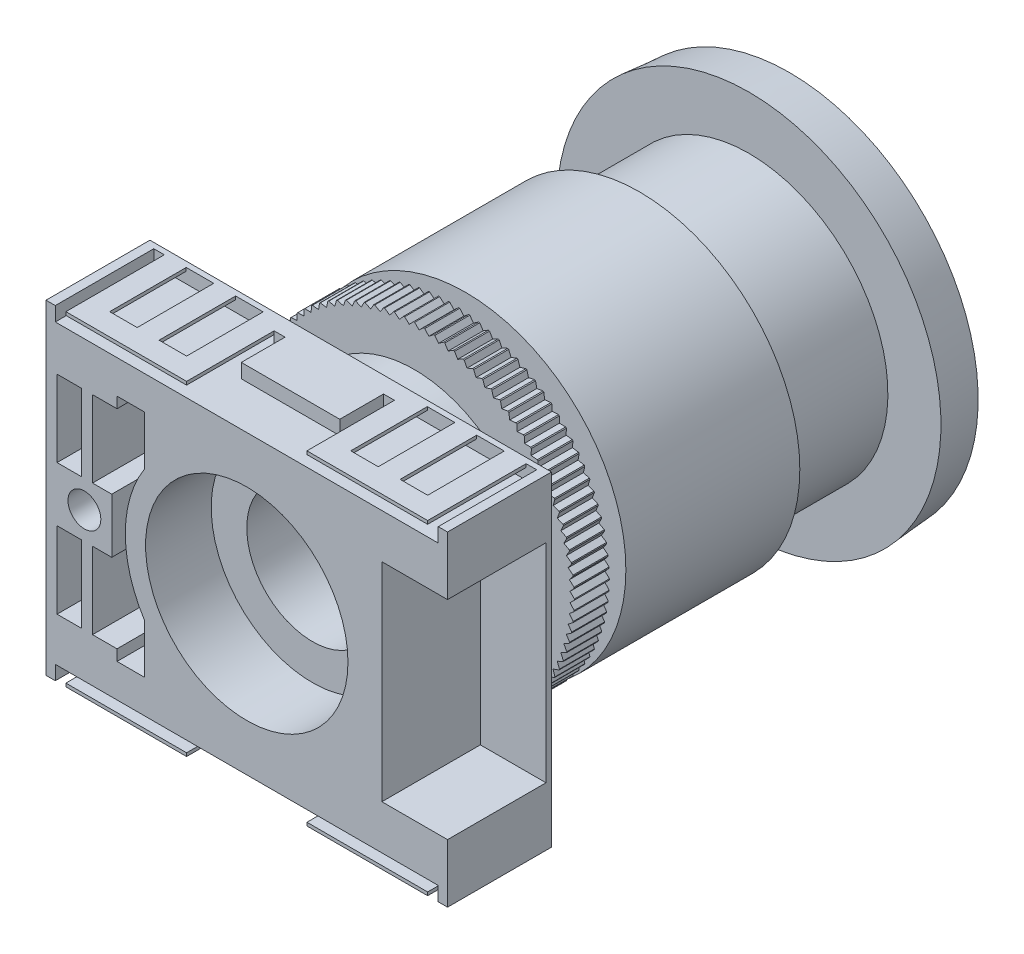
SolidWorks part; units mm, degrees
material "ABS"
ref_plane "正面" through (0, 0, 0) normal (0, 0, 1) x (1, 0, 0)
ref_plane "平面" through (0, 0, 0) normal (0, 1, 0) x (1, 0, 0)
ref_plane "右側面" through (0, 0, 0) normal (1, 0, 0) x (0, 0, -1)
sketch "ｽｹｯﾁ2" plane through (0, 0, 0) normal (1, 0, 0) x (0, 0, -1)
  line L0 (0, 0) -> (-50.6, 0) construction
  line L1 (-30.3, 0) -> (-30.3, 14.65)
  line L2 (-30.3, 14.65) -> (-14.4, 14.65)
  line L3 (-1.9, 15.9) -> (-0.7, 15.9)
  line L4 (-14.4, 12.8) -> (-14.4, 14.65)
  line L5 (-14.4, 12.7) -> (-4.4, 12.7)
  line L6 (-4.4, 12.7) -> (-4.4, 17.55)
  line L7 (-4.4, 17.55) -> (-0.7, 17.55) construction
  line L8 (-0.7, -13.9) -> (-0.7, 13.9) construction
  line L9 (-0.7, 17.25) -> (-4.4, 17.55)
  line L10 (-1.9, 13.9) -> (-0.7, 13.9)
  line L11 (-0.7, 15.9) -> (-0.7, 17.25)
  line L12 (-5.9513, 13.9) -> (1.3937, 13.9) construction
  line L13 (-5.9513, 15.9) -> (1.3937, 15.9) construction
  line L14 (-14.4, 12.7) -> (-28.4, 12.7)
  line L15 (-28.4, 12.7) -> (-28.4, 12.8)
  line L16 (-28.4, 12.8) -> (-14.4, 12.8)
  line L17 (0, 0) -> (-30.3, 0)
  arc A0 (-1.9, 15.9) -> (-1.9, 13.9) centre (-1.9, 14.9) ccw
  arc A1 (-0.7, 13.9) -> (0, 0) centre (-138.3571, 0) cw
  point P22 (-0.7, 0)
  dimension "D1" = 20.3
  dimension "D2" = 50.6
  dimension "D3" = 15.9
  dimension "D4" = 17.55
  dimension "D5" = 2
  dimension "D6" = 3.7
  dimension "D7" = 1.2
revolve "回転1" add sketch "ｽｹｯﾁ2" angle 360 about L0
sketch "ｽｹｯﾁ3" plane through (0, 0, 30.3) normal (0, 0, 1) x (1, 0, 0)
  circle A0 centre (0, 0) radius 10.9
extrude "ﾎﾞｽ - 押し出し1" add sketch "ｽｹｯﾁ3" along normal blind 20
sketch "ｽｹｯﾁ4" plane through (0, 0, 50.3) normal (0, 0, 1) x (1, 0, 0)
  circle A0 centre (0, 0) radius 6
extrude "ｶｯﾄ - 押し出し1" cut sketch "ｽｹｯﾁ4" against normal blind 49
sketch "ｽｹｯﾁ5" plane through (0, 0, 50.3) normal (0, 0, 1) x (1, 0, 0)
  circle A0 centre (0, 0) radius 9.25
extrude "ｶｯﾄ - 押し出し2" cut sketch "ｽｹｯﾁ5" against normal blind 6
ref_plane "平面2" through (0, 0, 31.8) normal (0, 0, 1) x (1, 0, 0)
sketch "ｽｹｯﾁ7" plane through (0, 0, 31.8) normal (0, 0, 1) x (1, 0, 0)
  circle A0 centre (0, 0) radius 14.7
  circle A1 centre (0, 0) radius 10.9
extrude "ﾎﾞｽ - 押し出し2" add sketch "ｽｹｯﾁ7" along normal blind 3.2
sketch "ｽｹｯﾁ9" plane through (0, 0, 35) normal (0, 0, 1) x (1, 0, 0)
  line L0 (0, 0) -> (0, 14.7) construction
  line L1 (0, 0) -> (0.923, 14.671) construction
  line L2 (0, 0) -> (0.4617, 14.6927) construction
  line L3 (0.4617, 14.6927) -> (0.4476, 14.243)
  line L4 (0.4476, 14.243) -> (0, 14.7)
  line L5 (0.4476, 14.243) -> (0.923, 14.671)
  circle A0 centre (0, 0) radius 14.7 construction
  arc A1 (0, 14.7) -> (0.923, 14.671) centre (0, 0) cw
  circle M1 centre (0, 0) radius 14.7
  dimension "D1" = 3.6
extrude "ｶｯﾄ - 押し出し3" cut sketch "ｽｹｯﾁ9" along direction (0, 0, 1) on the side against the normal up to next (3.2 mm away) contours L4 L3 M1 | L3 L5 M1 region at (0.6112, 14.5364, 35) region at (0.3027, 14.5461, 35)
pattern_circular "円形ﾊﾟﾀｰﾝ1" count 100 over 360 about axis through (0, 0, 35) along (0, 0, 1) of "ｶｯﾄ - 押し出し3"
sketch "ｽｹｯﾁ10" plane through (0, 0, 35) normal (0, 0, 1) x (1, 0, 0)
  circle A0 centre (0, 0) radius 14.65
extrude "ｶｯﾄ - 押し出し4" cut sketch "ｽｹｯﾁ10" against normal blind 3.2 flip side to cut
sketch "ｽｹｯﾁ11" plane through (0, 0, 50.3) normal (0, 0, 1) x (1, 0, 0)
  line L1 (18.35, 14.85) -> (-18.35, 14.85)
  line L2 (18.35, 14.85) -> (18.35, -14.85)
  line L3 (18.35, -14.85) -> (-18.35, -14.85)
  line L4 (-18.35, 14.85) -> (-18.35, -14.85)
  line L5 (18.35, 14.85) -> (-18.35, -14.85) construction
  line L6 (18.35, -14.85) -> (-18.35, 14.85) construction
  circle A0 centre (0, 0) radius 10.9 construction
  circle A1 centre (0, 0) radius 10.9
  point P0 (0, 0)
extrude "ﾎﾞｽ - 押し出し3" add sketch "ｽｹｯﾁ11" against normal blind 9.5
sketch "ｽｹｯﾁ13" plane through (0, 0, 50.3) normal (0, 0, 1) x (1, 0, 0)
  line L1 (18.35, 14.85) -> (-18.35, 14.85) construction
  line L2 (-17.5, 14.55) -> (-17.5, 13.55)
  line L3 (-17.5, 13.55) -> (17.5, 13.55)
  line L4 (17.5, 14.55) -> (17.5, 13.55)
  line L5 (-5.5, 16.15) -> (5.5, 16.15)
  line L6 (-0.5843, 13.55) -> (-9.5843, 13.55)
  line L7 (17.5, 14.55) -> (5.5, 14.55)
  line L8 (-5.5, 16.15) -> (-5.5, 14.55)
  line L9 (-5.5, 13.55) -> (5.5, 13.55)
  line L10 (5.5, 16.15) -> (5.5, 14.55)
  line L11 (-5.5, 14.55) -> (-17.5, 14.55)
  line L12 (-5.5, 16.15) -> (5.5, 13.55) construction
  line L13 (-5.5, 13.55) -> (5.5, 16.15) construction
  point P0 (0, 14.85)
extrude "ｶｯﾄ - 押し出し5" cut sketch "ｽｹｯﾁ13" against normal blind 9 contours L3 L4 L7 L10 L5 L8 L11 L2
sketch "ｽｹｯﾁ15" plane through (0, 13.55, 0) normal (0, 1, 0) x (-1, 0, 0)
  line L0 (-5.5, 41.3) -> (5.5, 41.3)
  line L1 (5.5, 41.3) -> (5.5, 42.3)
  line L2 (5.5, 41.3) -> (5.5, 50.3) construction
  line L3 (5.5, 42.3) -> (4.5, 42.3)
  line L4 (4.5, 42.3) -> (4.5, 46.3)
  line L5 (4.5, 46.3) -> (-4.5, 46.3)
  line L6 (-4.5, 46.3) -> (-4.5, 42.3)
  line L7 (-4.5, 42.3) -> (-5.5, 42.3)
  line L8 (-5.5, 41.3) -> (-5.5, 50.3) construction
  line L9 (-5.5, 42.3) -> (-5.5, 41.3)
extrude "ﾎﾞｽ - 押し出し5" add sketch "ｽｹｯﾁ15" along normal up to surface (1.3 mm away) up to face at (0, 14.85, 45.675)
sketch "ｽｹｯﾁ16" plane through (0, 14.85, 0) normal (0, 1, 0) x (1, 0, 0)
  line L4 (-7.5, -48.3) -> (-10.0166, -48.3)
  line L5 (18.35, -41.3) -> (-18.35, -41.3)
  line L6 (-7.5, -48.3) -> (-7.5, -42.3)
  line L7 (-16.35, -48.3) -> (-7.5, -48.3)
  line L8 (-16.35, -40.8) -> (-16.35, -48.3)
  line L9 (-7.5, -48.3) -> (-7.5, -41.3)
  line L10 (-14.5331, -48.3) -> (-12.0166, -48.3)
  line L11 (-16.5331, -50.3) -> (-17.5, -50.3)
  line L12 (-7.5, -41.3) -> (-10.0166, -41.3)
  line L19 (-14.5331, -48.3) -> (-14.5331, -41.3)
  line L20 (-12.0166, -41.3) -> (-14.5331, -41.3)
  line L21 (-16.5331, -50.3) -> (-16.5331, -41.3)
  line L22 (-5.5, -50.3) -> (-16.5331, -50.3) construction
  line L23 (-5.5, -50.3) -> (-5.5, -41.3) construction
  line L24 (-12.0166, -48.3) -> (-14.5331, -48.3)
  line L25 (-10.0166, -41.3) -> (-10.0166, -48.3)
  line L26 (-17.5, -50.3) -> (-17.5, -41.3)
  line L27 (-12.0166, -41.3) -> (-12.0166, -48.3)
  line L28 (-17.5, -41.3) -> (-16.5331, -41.3)
  line L30 (-10.0166, -48.3) -> (-7.5, -48.3)
  line L31 (-7.5, -48.3) -> (-14.5331, -48.3) construction
  line M16 (-18.35, -50.3) -> (-5.5, -50.3)
  dimension "D3" = 2
  dimension "D1" = 2
  dimension "D2" = 0.5
extrude "ｶｯﾄ - 押し出し6" cut sketch "ｽｹｯﾁ16" against normal up to next contours L28 L26 L21 M16 | L27 L20 L19 L10 | L12 L25 L4 L9 region at (-17.0166, 14.85, 45.8) region at (-8.7583, 14.85, 44.8) region at (-13.2748, 14.85, 44.8)
mirror "ﾐﾗｰ1" about plane through (0, 0, 0) normal (1, 0, 0) of "ｶｯﾄ - 押し出し6"
mirror "ﾐﾗｰ2" about plane through (0, 0, 0) normal (0, 1, 0) of "ｶｯﾄ - 押し出し5"
sketch "ｽｹｯﾁ17" plane through (0, -13.55, 0) normal (0, -1, 0) x (1, 0, 0)
  line L0 (-5.5, 41.3) -> (5.5, 41.3)
  line L1 (5.5, 41.3) -> (5.5, 42.3)
  line L2 (5.5, 41.3) -> (5.5, 50.3) construction
  line L3 (5.5, 42.3) -> (4.5, 42.3)
  line L4 (4.5, 42.3) -> (4.5, 47.3)
  line L5 (4.5, 47.3) -> (-4.5, 47.3)
  line L6 (-4.5, 47.3) -> (-4.5, 42.3)
  line L7 (-4.5, 42.3) -> (-5.5, 42.3)
  line L8 (-5.5, 41.3) -> (-5.5, 50.3) construction
  line L9 (-5.5, 42.3) -> (-5.5, 41.3)
extrude "ﾎﾞｽ - 押し出し6" add sketch "ｽｹｯﾁ17" along normal up to vertex (1.3 mm away) up to point (-5.5, -14.85, 41.3)
mirror "ﾐﾗｰ4" about plane through (0, 0, 0) normal (0, 1, 0) of "ﾐﾗｰ1", "ｶｯﾄ - 押し出し6"
sketch "ｽｹｯﾁ18" plane through (0, 0, 50.3) normal (0, 0, 1) x (1, 0, 0)
  line L0 (18.35, 0) -> (13.35, 0) construction
  line L1 (18.35, -14.85) -> (18.35, 14.85) construction
  line L2 (-18.35, 0) -> (-13.3397, 0) construction
  line L3 (18.35, 9.5) -> (13.35, 9.5)
  line L4 (18.35, 9.5) -> (18.35, -9.5)
  line L5 (18.35, -9.5) -> (13.35, -9.5)
  line L6 (13.35, 9.5) -> (13.35, -9.5)
  line L7 (18.35, 9.5) -> (13.35, -9.5) construction
  line L8 (18.35, -9.5) -> (13.35, 9.5) construction
  line L10 (-18.35, 14.85) -> (-18.35, -14.85) construction
  line L11 (-18.35, 0) -> (-14.5997, 0) construction
  line L12 (-11.8597, -10.5) -> (-9.3397, -10.5)
  line L13 (-17.3397, -9.5) -> (-17.3397, 9.5)
  line L14 (-11.8597, 10.5) -> (-9.3397, 10.5)
  line L15 (-9.3397, -10.5) -> (-9.3397, -6)
  line L16 (-11.8597, 9.5) -> (-11.8597, 10.5)
  line L17 (-11.8597, -9.5) -> (-11.8597, -10.5)
  line L18 (-14.5997, 9.5) -> (-14.5997, -9.5) construction
  line L19 (-11.8597, 9.5) -> (-14.0997, 9.5)
  line L20 (-17.3397, -2.5) -> (-12.3397, -2.5)
  line L21 (-11.8597, -9.5) -> (-14.0997, -9.5)
  line L23 (-15.0997, 9.5) -> (-15.0997, 2.5)
  line L24 (-14.0997, 9.5) -> (-14.0997, 2.5)
  line L25 (-15.0997, 9.5) -> (-17.3397, 9.5)
  line L26 (-15.0997, -9.5) -> (-17.3397, -9.5)
  line L27 (-17.3397, 2.5) -> (-12.3397, 2.5)
  line L28 (-14.0997, -2.5) -> (-14.0997, -9.5)
  line L29 (-18.35, 2.5) -> (-13.3397, 2.5) construction
  line L30 (-18.35, -2.5) -> (-13.3397, -2.5) construction
  line L31 (-15.0997, -2.5) -> (-15.0997, -9.5)
  line L32 (-14.0997, 9.5) -> (-14.0997, -9.5) construction
  line L33 (-12.3397, 2.5) -> (-12.3397, -2.5)
  line L34 (-15.0997, 9.5) -> (-15.0997, -9.5) construction
  line L35 (-12.3397, 2.5) -> (-17.3397, -2.5) construction
  line L36 (-10.3104, 6) -> (-7.9462, 6) construction
  line L37 (-9.3397, 6) -> (-9.3397, 10.5)
  circle A0 centre (-14.8397, 0) radius 1.5
  arc A1 (-9.3397, 6) -> (-9.3397, -6) centre (0, 0) ccw
  point P5 (15.85, 0)
  dimension "D6" = 4.5
  dimension "D1" = 0.5
  dimension "D2" = 0.5
  dimension "D5" = 5
  dimension "D3" = 2.5
  dimension "D4" = 2.5
extrude "ｶｯﾄ - 押し出し7" cut sketch "ｽｹｯﾁ18" against normal blind 9 contours L13 L27 L23 L25 | A1 L37 L14 L16 L19 L24 L27 L33 L20 L28 L21 L17 L12 L15 | L31 L20 L13 L26 | A0 region at (-11.7901, 0, 50.3) region at (-16.2197, -6, 50.3) region at (-16.2197, 6, 50.3) region at (-14.8397, 0, 50.3)
sketch "ｽｹｯﾁ19" plane through (0, 0, 50.3) normal (0, 0, 1) x (1, 0, 0)
  line L0 (18.35, 0) -> (15.35, 0) construction
  line L1 (18.35, -14.85) -> (18.35, 14.85) construction
  line L3 (12.35, -9.5) -> (18.35, -9.5)
  line L4 (12.35, -9.5) -> (12.35, 9.5)
  line L5 (12.35, 9.5) -> (18.35, 9.5)
  line L6 (18.35, -9.5) -> (18.35, 9.5)
  line L7 (12.35, -9.5) -> (18.35, 9.5) construction
  line L8 (12.35, 9.5) -> (18.35, -9.5) construction
extrude "ｶｯﾄ - 押し出し8" cut sketch "ｽｹｯﾁ19" against normal blind 9
